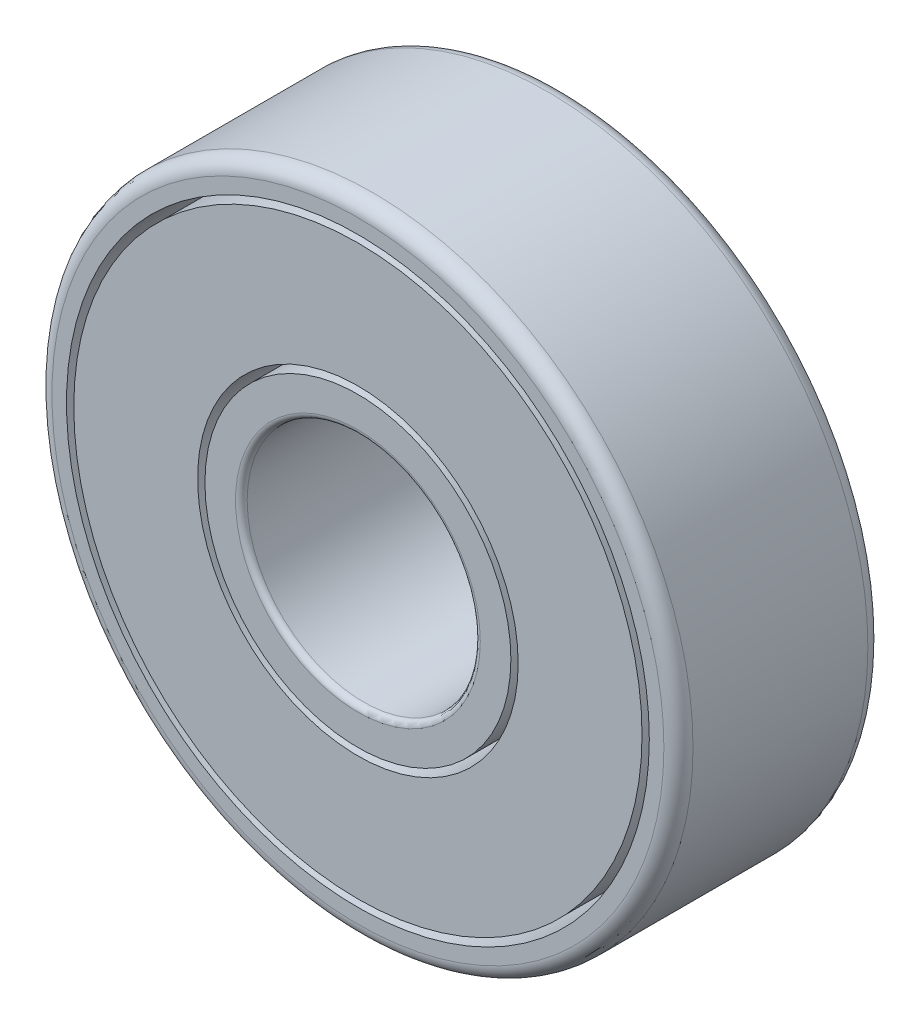
SolidWorks part; units mm, degrees
material "AISI 304"
ref_plane "Alzado" through (0, 0, 0) normal (0, 0, 1) x (1, 0, 0)
ref_plane "Planta" through (0, 0, 0) normal (0, 1, 0) x (1, 0, 0)
ref_plane "Vista lateral" through (0, 0, 0) normal (1, 0, 0) x (0, 0, -1)
sketch "Croquis1" plane through (0, 0, 0) normal (0, 0, 1) x (1, 0, 0)
  circle A0 centre (0, 0) radius 4
  circle A1 centre (0, 0) radius 5.25
  circle A2 centre (0, 0) radius 5.5
  circle A3 centre (0, 0) radius 9.75
  circle A4 centre (0, 0) radius 10
  circle A5 centre (0, 0) radius 11
  dimension "D1" = 22
  dimension "D2" = 8
  dimension "D3" = 11
  dimension "D4" = 20
  dimension "D5" = 10.5
  dimension "D6" = 19.5
extrude "Saliente-Extruir1" add sketch "Croquis1" along normal blind 7 contours A3 A2 | A1 A0 | A5 A4 region at (-5.1015, 0, 0) region at (-9.4742, 0, 0) region at (-10.6889, 0, 0)
fillet "Redondeo1" radius 0.2 2 edges at (4, 0, 0) (4, 0, 7)
fillet "Redondeo2" radius 0.5 2 edges at (11, 0, 0) (11, 0, 7)
